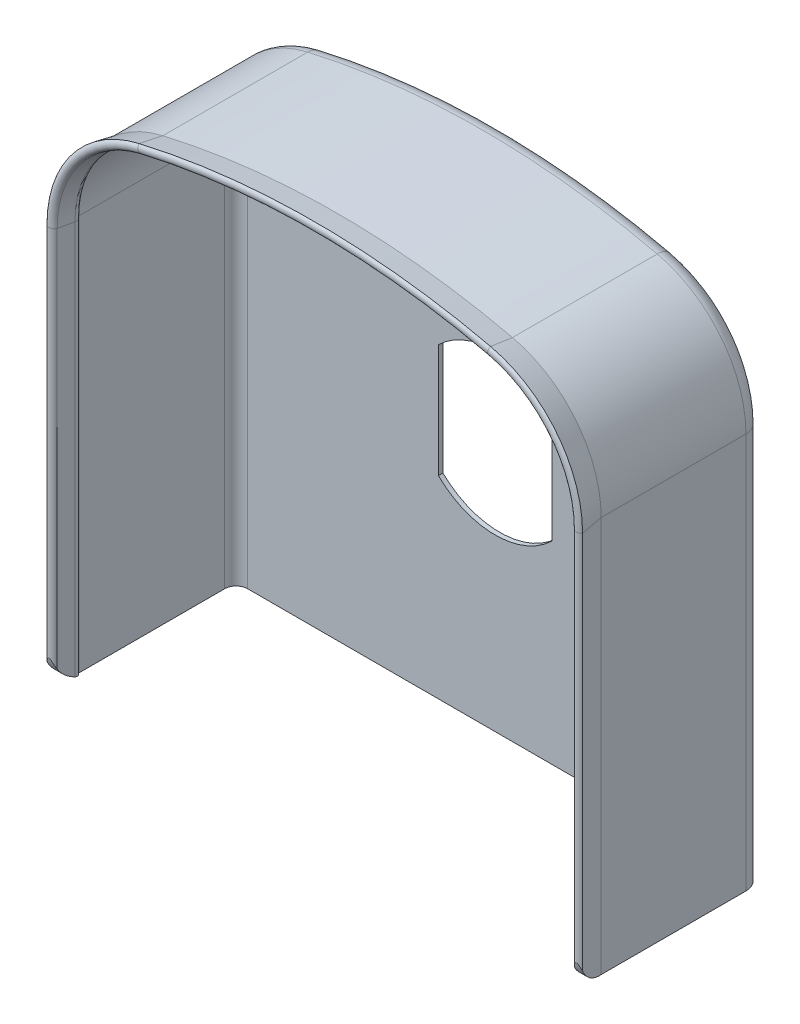
SolidWorks part; units mm, degrees
ref_plane "Plano frontal" through (0, 0, 0) normal (0, 0, 1) x (1, 0, 0)
ref_plane "Plano superior" through (0, 0, 0) normal (0, 1, 0) x (1, 0, 0)
ref_plane "Plano direito" through (0, 0, 0) normal (1, 0, 0) x (0, 0, -1)
sketch "Esboço1" plane through (0, 0, 0) normal (0, 0, 1) x (1, 0, 0)
  line L0 (0, 0) -> (0, 69.0964)
  line L1 (-92, 84) -> (0, 84) construction
  line L2 (-92, 69.0964) -> (-92, 0)
  line L3 (-46, 84) -> (-46, 92) construction
  arc A0 (-76.5168, 88.5797) -> (-15.4832, 88.5797) centre (-46, -43.0549) cw
  arc A1 (0, 69.0964) -> (-15.4832, 88.5797) centre (-20, 69.0964) ccw
  arc A2 (-92, 69.0964) -> (-76.5168, 88.5797) centre (-72, 69.0964) cw
  dimension "D4" = 20
  dimension "D1" = 8
  dimension "D2" = 92
  dimension "D3" = 92
sketch "Esboço2" plane through (0, 0, 0) normal (0, 1, 0) x (1, 0, 0)
  line L0 (-0.8, -28.2733) -> (-0.0929, -32.0442)
  line L2 (0, 0) -> (0, -28.2733)
  line L3 (-0.8, -28.2733) -> (-0.8, 0)
  line L4 (-92, 0) -> (0, 0) construction
  line L5 (-0.8, 0) -> (0, 0)
  line L7 (0, -28.2733) -> (0.75, -32.2733)
  line L8 (-0.0929, -32.0442) -> (-0.8307, -28.4014)
  line L9 (-0.8307, -28.4014) -> (-1.5334, -28.5437)
  line L10 (-1.5334, -28.5437) -> (-0.8, -32.0442)
  arc A0 (0.75, -32.2733) -> (-0.8, -32.0442) centre (0.0391, -31.7248) cw
  dimension "D1" = 0.8
sweep "Varredura1" add profiles "Esboço2" path "Esboço1"
sketch "Esboço4" plane through (0, 0, 0) normal (0, 0, -1) x (-1, 0, 0)
  line L1 (92, 0) -> (0, 0)
  line L2 (92, 0) -> (92, 99.397)
  line L3 (92, 99.397) -> (0, 99.397)
  line L4 (0, 0) -> (0, 99.397)
extrude "Ressalto-extrusão2" add sketch "Esboço4" against normal blind 0.8
sketch "Esboço6" plane through (0, 0, 0.8) normal (0, 0, 1) x (1, 0, 0)
  line L0 (-92, 69.0964) -> (-92, 105.834)
  line L1 (-92, 105.834) -> (0, 105.834)
  line L2 (0, 105.834) -> (0, 69.0964)
  arc A1 (0, 69.0964) -> (-15.4832, 88.5797) centre (-20, 69.0964) ccw
  arc A2 (-15.4832, 88.5797) -> (-76.5168, 88.5797) centre (-46, -43.0549) ccw
  arc A3 (-92, 69.0964) -> (-76.5168, 88.5797) centre (-72, 69.0964) cw
extrude "Corte-extrusão1" cut sketch "Esboço6" against normal blind 1
sketch "Esboço7" plane through (0, 0, 0) normal (0, 0, -1) x (-1, 0, 0)
  line L0 (46, 0) -> (46, 43.65) construction
  line L1 (0, 0) -> (92, 0) construction
  line L2 (55.9, 53.55) -> (55.9, 33.75)
  line L3 (36.1, 53.55) -> (36.1, 33.75)
  line L4 (36.1, 53.55) -> (55.9, 53.55) construction
  line L5 (46, 53.55) -> (46, 57.55) construction
  line L6 (46, 43.65) -> (106.0275, 43.65) construction
  arc A0 (36.1, 53.55) -> (55.9, 53.55) centre (46, 43.3546) cw
  arc A1 (36.1, 33.75) -> (55.9, 33.75) centre (46, 43.9454) ccw
  dimension "D1" = 43.65
  dimension "D2" = 4
extrude "Corte-extrusão2" cut sketch "Esboço7" against normal through all
fillet "Filete8" radius 1 5 edges at (-46, 90.5374, 28.5437) (-86.4574, 80.5856, 28.5437) (-90.4666, 34.5482, 28.5437) (-5.5426, 80.5856, 28.5437) (-1.5334, 34.5482, 28.5437)
sketch "Esboço8" plane through (0, 0, 0) normal (1, 0, 0) x (0, 0, -1)
  line L0 (-14.1367, 0) -> (-28.2733, 0)
  line L1 (-28.2733, 0) -> (0, 0) construction
  line L2 (-32.6227, 69.0964) -> (-32.6227, 0) construction
  line L3 (-32.6227, 4) -> (-38.4698, 4)
  line L4 (-38.4698, 4) -> (-38.4698, -4.5735)
  line L5 (-38.4698, -4.5735) -> (-14.1367, -4.5735)
  line L6 (-14.1367, -4.5735) -> (-14.1367, 0)
  arc A0 (-28.2733, 0) -> (-32.6227, 4) centre (-27.7175, 4.969) cw
  dimension "D2" = 5
  dimension "D1" = 4
extrude "Corte-extrusão4" cut sketch "Esboço8" against normal through all and the other way through all
fillet "Filete10" radius 2 5 edges at (-91.2, 34.5482, 0.8) (-87.0315, 81.0419, 0.8) (-46, 91.2708, 0.8) (-0.8, 34.5482, 0.8) (-4.9685, 81.0419, 0.8)
fillet "Filete11" radius 3 5 edges at (0, 34.5482, 0) (-4.3422, 81.5396, 0) (-92, 34.5482, 0) (-46, 92.0708, 0) (-87.6578, 81.5396, 0)
